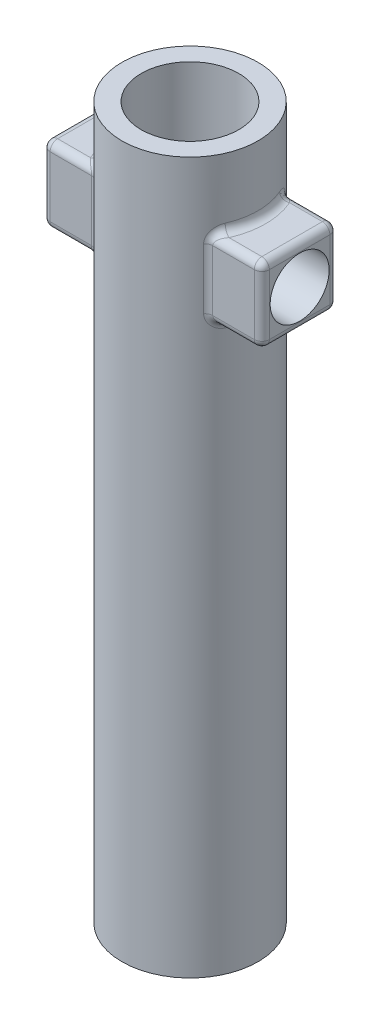
SolidWorks part; units mm, degrees
ref_plane "Front Plane" through (0, 0, 0) normal (0, 0, 1) x (1, 0, 0)
ref_plane "Top Plane" through (0, 0, 0) normal (0, 1, 0) x (1, 0, 0)
ref_plane "Right Plane" through (0, 0, 0) normal (1, 0, 0) x (0, 0, -1)
sketch "Sketch1" plane through (0, 0, 0) normal (0, 1, 0) x (1, 0, 0)
  circle A0 centre (0, 0) radius 3
  circle A1 centre (0, 0) radius 4.5
  dimension "D1" = 6
  dimension "D2" = 9
extrude "main_body" add sketch "Sketch1" along normal blind 20
ref_plane "Plane2" through (0, 40, 0) normal (0, -1, 0) x (-1, 0, 0)
sketch "Sketch2" plane through (0, 20, 0) normal (0, 1, 0) x (1, 0, 0)
  circle A0 centre (0, 0) radius 4.5
  dimension "D1" = 9
extrude "slider_shaft" add sketch "Sketch2" along normal blind 2
sketch "Sketch3" plane through (0, 22, 0) normal (0, 1, 0) x (1, 0, 0)
  circle A0 centre (0, 0) radius 3.225
  circle A1 centre (0, 0) radius 4.5
  dimension "D1" = 6.45
  dimension "D2" = 9
extrude "main_body2" add sketch "Sketch3" along normal blind 25
sketch "Sketch4" plane through (0, 40, 0) normal (0, 1, 0) x (1, 0, 0)
  line L1 (7.25, -2.5) -> (-7.25, -2.5)
  line L2 (7.25, -2.5) -> (7.25, 2.5)
  line L3 (7.25, 2.5) -> (-7.25, 2.5)
  line L4 (-7.25, -2.5) -> (-7.25, 2.5)
  circle A0 centre (0, 0) radius 3.225 construction
  circle A1 centre (0, 0) radius 4.5
  dimension "D5" = 9
  dimension "D1" = 14.5
  dimension "D2" = 7.25
  dimension "D3" = 5
  dimension "D4" = 2.5
extrude "axle_base" add sketch "Sketch4" along normal blind 2.5 and the other way blind 2.5 contours L1 A1 L3 L2 | L3 A1 L1 L4 region at (5.7449, 40, 0) region at (-5.7449, 40, 0)
sketch "Sketch8" plane through (7.25, 0, 0) normal (1, 0, 0) x (0, 0, -1)
  line L1 (-2.5, 42.5) -> (2.5, 42.5) construction
  line L2 (2.5, 37.5) -> (2.5, 42.5) construction
  circle A0 centre (0, 40) radius 1.95
  dimension "D1" = 3.9
  dimension "D2" = 2.5
  dimension "D3" = 2.5
extrude "dowel_mount" cut sketch "Sketch8" against normal blind 3.5
sketch "Sketch5" plane through (7.25, 0, 0) normal (1, 0, 0) x (0, 0, -1)
  line L1 (2.5, 37.5) -> (2.5, 42.5) construction
  line L2 (-2.5, 42.5) -> (2.5, 42.5) construction
  circle A0 centre (0, 40) radius 2
  dimension "D1" = 4
  dimension "D3" = 2.5
  dimension "D2" = 2.5
ref_plane "Plane1" through (0, 0, 0) normal (1, 0, 0) x (0, 0, -1)
sketch "Sketch7" plane through (0, 22, 0) normal (0, 1, 0) x (1, 0, 0)
  circle A0 centre (0, 0) radius 2.5
  dimension "D1" = 5
fillet "axle_base_fillet" radius 0.5 24 edges at (7.25, 37.5, 0) (4.5, 37.5, 0) (5.4958, 37.5, 2.5) (3.7417, 40, 2.5) (7.25, 40, 2.5) (4.5, 42.5, 0) (7.25, 42.5, 0) (5.4958, 42.5, 2.5) (5.4958, 37.5, -2.5) (7.25, 40, -2.5) (5.4958, 42.5, -2.5) (3.7417, 40, -2.5) (-7.25, 37.5, 0) (-4.5, 37.5, 0) (-7.25, 40, -2.5) (-5.4958, 37.5, -2.5) (-3.7417, 40, -2.5) (-3.7417, 40, 2.5) (-5.4958, 37.5, 2.5) (-7.25, 40, 2.5) (-4.5, 42.5, 0) (-5.4958, 42.5, 2.5) (-7.25, 42.5, 0) (-5.4958, 42.5, -2.5)
extrude "slider_shaft_cut" cut sketch "Sketch3<2>" against normal blind 2 flip side to cut
sketch "Sketch3<2>" plane through (0, 22, 0) normal (0, 1, 0) x (1, 0, 0) same geometry as "Sketch3"
mirror "Mirror1" about plane through (0, 0, 0) normal (1, 0, 0) of "dowel_mount"
